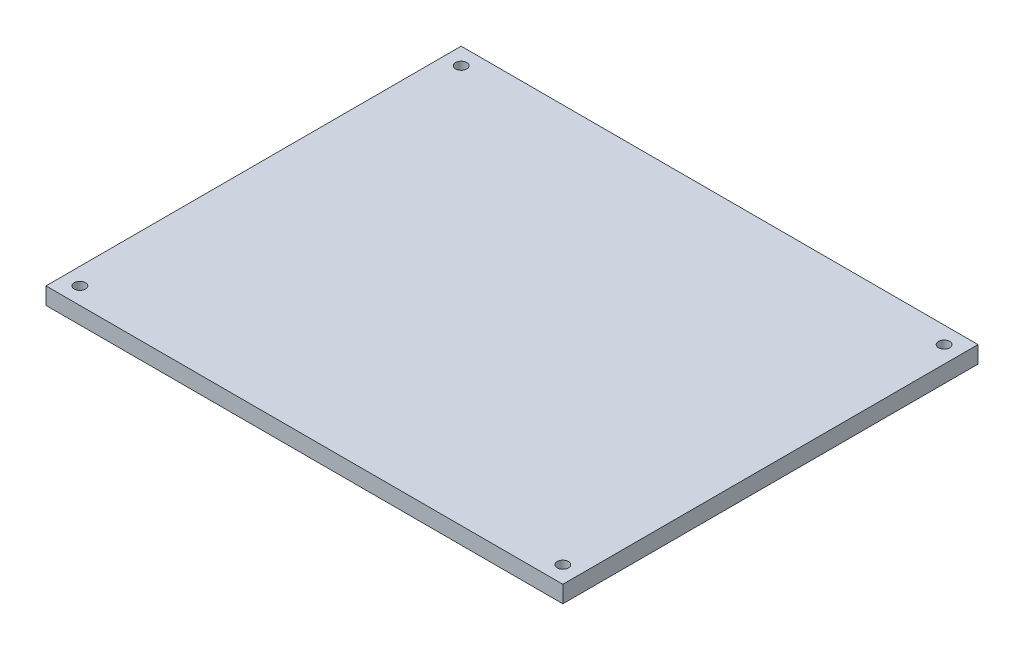
SolidWorks part; units mm, degrees
ref_plane "Front Plane" through (0, 0, 0) normal (0, 0, 1) x (1, 0, 0)
ref_plane "Top Plane" through (0, 0, 0) normal (0, 1, 0) x (1, 0, 0)
ref_plane "Right Plane" through (0, 0, 0) normal (1, 0, 0) x (0, 0, -1)
other "Configuration Table"
sketch "Sketch1" plane through (0, 0, 0) normal (1, 0, 0) x (0, 0, -1)
  line L1 (110, -10) -> (-135, -10)
  line L2 (110, -10) -> (110, 0)
  line L3 (110, 0) -> (-135, 0)
  line L4 (-135, -10) -> (-135, 0)
  line L5 (110, -10) -> (-135, 0) construction
  line L6 (110, 0) -> (-135, -10) construction
extrude "plate" add sketch "Sketch1" along normal blind 305 from offset 40 separate body offset against normal yes
sketch "Sketch2" plane through (0, 0, 0) normal (0, 1, 0) x (1, 0, 0)
  circle A0 centre (-30, 100) radius 3.3
extrude "h0" add sketch "Sketch2" along normal blind 14 from offset 12 separate body offset against normal yes
combine bodies "Combine1" operation type subtract main body 102 bodies to subtract 103
sketch "Sketch3" plane through (0, 0, 0) normal (0, 1, 0) x (1, 0, 0)
  circle A0 centre (-30, -125) radius 3.3
extrude "h1" add sketch "Sketch3" along normal blind 14 from offset 12 separate body offset against normal yes
combine bodies "Combine2" operation type subtract main body 104 bodies to subtract 105
sketch "Sketch4" plane through (0, 0, 0) normal (0, 1, 0) x (1, 0, 0)
  circle A0 centre (255, 100) radius 3.3
extrude "h2" add sketch "Sketch4" along normal blind 14 from offset 12 separate body offset against normal yes
combine bodies "Combine3" operation type subtract main body 106 bodies to subtract 107
sketch "Sketch5" plane through (0, 0, 0) normal (0, 1, 0) x (1, 0, 0)
  circle A0 centre (255, -125) radius 3.3
extrude "h3" add sketch "Sketch5" along normal blind 14 from offset 12 separate body offset against normal yes
combine bodies "Combine4" operation type subtract main body 108 bodies to subtract 109
